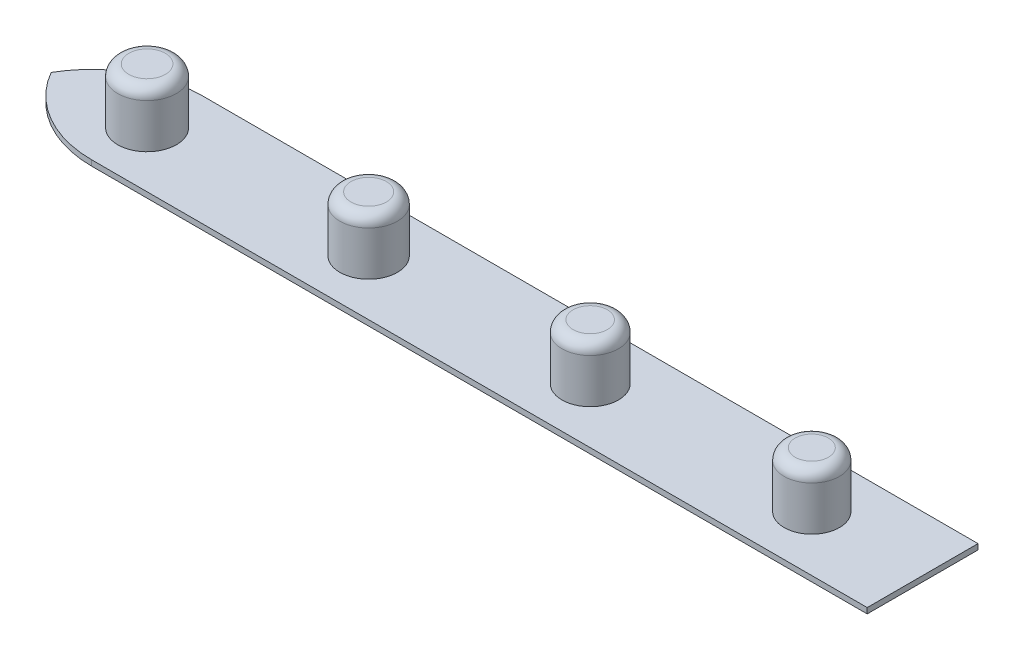
SolidWorks part; units mm, degrees
ref_plane "Front Plane" through (0, 0, 0) normal (0, 0, 1) x (1, 0, 0)
ref_plane "Top Plane" through (0, 0, 0) normal (0, 1, 0) x (1, 0, 0)
ref_plane "Right Plane" through (0, 0, 0) normal (1, 0, 0) x (0, 0, -1)
sketch "Sketch2" plane through (0, 0, 0) normal (0, 1, 0) x (1, 0, 0)
  line L0 (-40, 0) -> (40, 0) construction
  line L1 (-40, 5) -> (40, 5)
  line L2 (-40, 5) -> (-40, -5)
  line L3 (-40, -5) -> (40, -5)
  line L4 (40, 5) -> (40, -5)
  line L5 (-40, 5) -> (40, -5) construction
  line L6 (-40, -5) -> (40, 5) construction
  point P0 (0, 0)
  dimension "D1" = 80
  dimension "D2" = 10
extrude "Boss-Extrude1" add sketch "Sketch2" along normal blind 0.5
sketch "Sketch3" plane through (0, 0.5, 0) normal (0, 1, 0) x (1, 0, 0)
  line L0 (-40, 0) -> (40, 0) construction
  line L1 (-40, 5) -> (-40, -5) construction
  line L2 (40, -5) -> (40, 5) construction
  circle A0 centre (-30, 0) radius 2.65
  circle A1 centre (-10, 0) radius 2.6
  circle A2 centre (10, 0) radius 2.55
  circle A3 centre (30, 0) radius 2.5
  dimension "D5" = 5.3
  dimension "D6" = 5.2
  dimension "D7" = 5.1
  dimension "D8" = 5
  dimension "D1" = 10
  dimension "D2" = 20
  dimension "D3" = 20
  dimension "D4" = 20
extrude "Boss-Extrude2" add sketch "Sketch3" along normal blind 5
fillet "Fillet1" radius 1 4 edges at (30, 5.5, 2.5) (10, 5.5, 2.55) (-10, 5.5, 2.6) (-30, 5.5, 2.65)
fillet "Fillet2" radius 10 2 edges at (-40, 0.25, -5) (-40, 0.25, 5)
